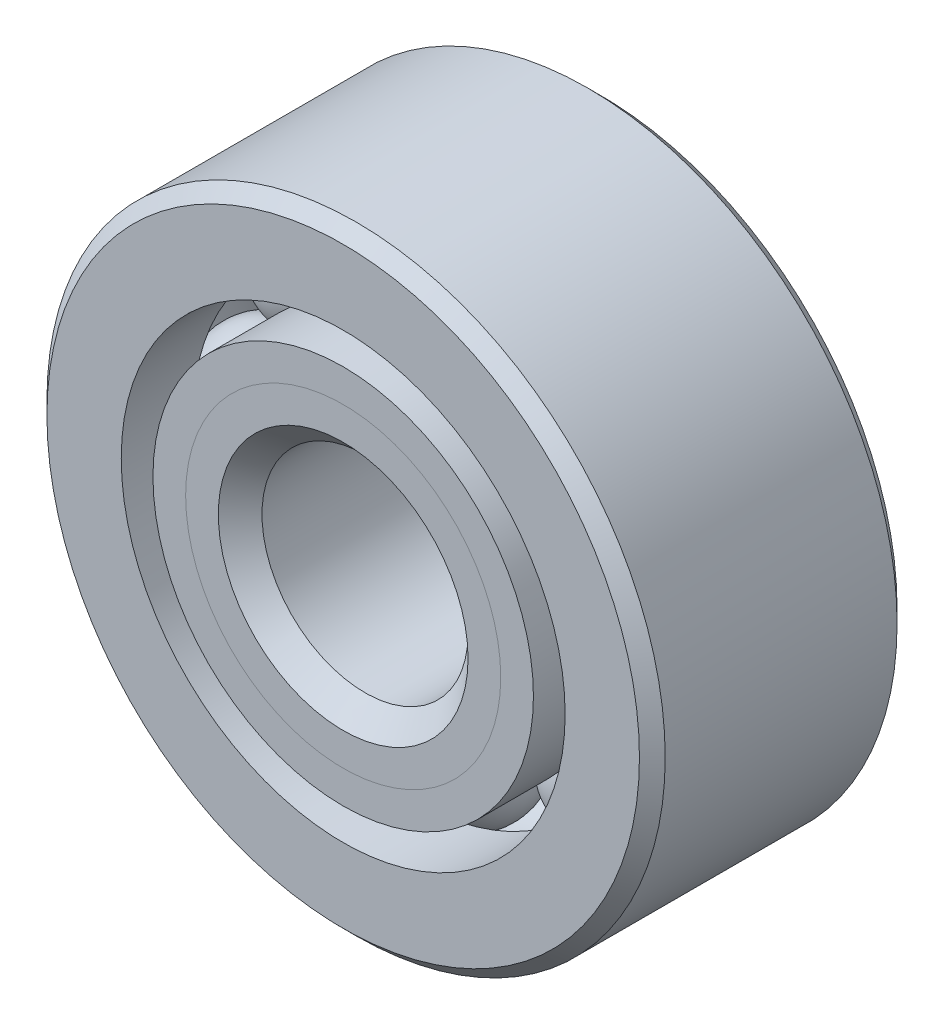
SolidWorks part; units mm, degrees
ref_plane "Front Plane" through (0, 0, 0) normal (0, 0, 1) x (1, 0, 0)
ref_plane "Top Plane" through (0, 0, 0) normal (0, 1, 0) x (1, 0, 0)
ref_plane "Right Plane" through (0, 0, 0) normal (1, 0, 0) x (0, 0, -1)
sketch "Sketch1" plane through (0, 0, 0) normal (1, 0, 0) x (0, 0, -1)
  line L0 (-1.9844, 0) -> (1.9844, 0) construction
  line L1 (0, 4.7625) -> (0, -4.7625) construction
  line L2 (1.7859, 4.7625) -> (-1.7859, 4.7625)
  line L3 (-1.7859, 4.7625) -> (-1.9844, 4.5641)
  line L4 (-1.9844, 4.5641) -> (-1.9844, 3.4192)
  line L5 (-1.9844, 3.4192) -> (-0.8819, 3.4192)
  line L6 (1.9844, 3.4192) -> (0.8819, 3.4192)
  line L7 (1.9844, 4.5641) -> (1.9844, 3.4192)
  line L8 (1.7859, 4.7625) -> (1.9844, 4.5641)
  line L9 (0, 4.7625) -> (0, 3.175) construction
  line L10 (0, 3.175) -> (0, 1.5875) construction
  arc A0 (-0.8819, 3.4192) -> (0.8819, 3.4192) centre (0, 3.175) cw
  point P14 (0, 1.5875)
  dimension "D3" = 1.7639
  dimension "D1" = 45
  dimension "Width" = 3.9688
  dimension "OD" = 9.525
  dimension "D2" = 0.1984
  dimension "Shaft Dia" = 3.175
  dimension "D4" = 0.2442
revolve "Revolve1" add sketch "Sketch1" angle 360 about L0
sketch "Sketch2" plane through (0, 0, 0) normal (1, 0, 0) x (0, 0, -1)
  line L0 (-1.9844, 2.9308) -> (-0.8819, 2.9308)
  line L1 (-1.9844, 4.5641) -> (-1.9844, -4.5641) construction
  line L2 (-1.9844, 2.9308) -> (-1.9844, 2.4272)
  line L3 (-1.9844, 2.4272) -> (-1.4808, 1.9237)
  line L4 (-1.4808, 1.9237) -> (0, 1.9237)
  line L5 (0, 4.7625) -> (0, -4.7625) construction
  line L6 (0, 1.9237) -> (0, 2.2599)
  line L7 (0, 2.2599) -> (0, 1.5875) construction
  line L8 (-1.9844, 2.9308) -> (-1.9844, 1.9237) construction
  line L9 (-1.9844, 1.9237) -> (-1.4808, 1.9237) construction
  arc A0 (-0.8819, 2.9308) -> (0, 2.2599) centre (0, 3.175) ccw
  arc A1 (0.8819, 3.4192) -> (-0.8819, 3.4192) centre (0, 3.175) ccw construction
  circle A2 centre (0, 3.175) radius 0.9151 construction
  dimension "D1" = 45
revolve "Revolve2" add sketch "Sketch2" angle 360 about L0
sketch "Sketch3" plane through (0, 0, 0) normal (1, 0, 0) x (0, 0, -1)
  line L0 (-1.9844, 2.4272) -> (-1.4808, 1.9237)
  line L1 (-1.4808, 1.9237) -> (0, 1.9237)
  line L2 (0, 1.9237) -> (0, 2.2599)
  line L3 (-1.9844, 2.4272) -> (-1.9844, 1.9237)
  line L4 (-1.9844, 2.9308) -> (-1.9844, 1.9237) construction
  line L5 (-1.9844, 1.9237) -> (-1.6482, 1.5875)
  line L6 (-1.6482, 1.5875) -> (1.7859, 1.5875)
  line L7 (1.7859, 4.7625) -> (1.7859, -4.7625) construction
  line L8 (1.7859, 1.5875) -> (1.9844, 1.7859)
  line L9 (1.9844, -4.5641) -> (1.9844, 4.5641) construction
  line L10 (1.9844, 1.7859) -> (1.9844, 2.9308)
  line L11 (1.9844, 2.9308) -> (0.8819, 2.9308)
  line L13 (1.7859, 4.7625) -> (1.9844, 4.5641) construction
  circle A0 centre (0, 3.175) radius 0.9151 construction
  arc A1 (0.8819, 2.9308) -> (0, 2.2599) centre (0, 3.175) cw
revolve "Revolve3" add sketch "Sketch3" angle 360 about L0
sketch "Sketch4" plane through (0, 0, 0) normal (1, 0, 0) x (0, 0, -1)
  line L0 (-0.9151, 3.175) -> (0.9151, 3.175)
  circle A1 centre (0, 3.175) radius 0.9151 construction
  arc A2 (-0.9151, 3.175) -> (0.9151, 3.175) centre (0, 3.175) cw
  arc A3 (0.8819, 3.4192) -> (-0.8819, 3.4192) centre (0, 3.175) ccw construction
revolve "Revolve4" add sketch "Sketch4" angle 360 about L0
ref_axis "Axis1" through (0, 0, -1.9844) along (0, 0, 1)
pattern_circular "CirPattern1" count 8 every 45 about axis through (0, 0, -1.9844) along (0, 0, 1) of bodies 104
equation "\"D2@Sketch1\" = \"Width@Sketch1\"*.05"
equation "\"D3@Sketch1\" = \"Width@Sketch1\"/2.25"
equation "\"D4@Sketch1\" = (((\"OD@Sketch1\"-\"Width@Sketch1\")/2)/3.25)/3.5"
equation "\"D2@CirPattern1\" = 360/\"Balls@CirPattern1\""
